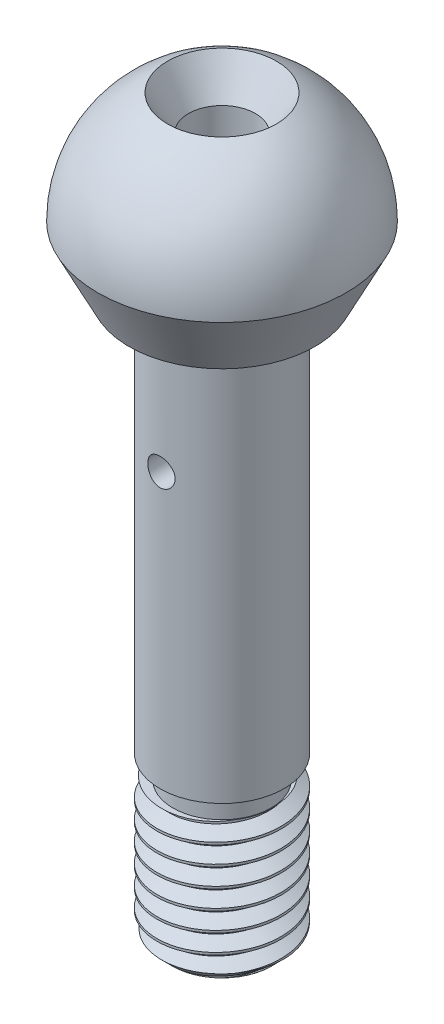
SolidWorks part; units mm, degrees
ref_plane "Front Plane" through (0, 0, 0) normal (0, 0, 1) x (1, 0, 0)
ref_plane "Top Plane" through (0, 0, 0) normal (0, 1, 0) x (1, 0, 0)
ref_plane "Right Plane" through (0, 0, 0) normal (1, 0, 0) x (0, 0, -1)
sketch "Sketch2" plane through (0, 0, 0) normal (0, 0, 1) x (1, 0, 0)
  line L0 (0, 12.7) -> (0, -63.5)
  line L1 (12.7, 0) -> (9.525, 0) construction
  line L2 (0, 0) -> (9.525, 0) construction
  line L3 (12.7, 0) -> (9.525, -6.35)
  line L5 (9.525, 0) -> (9.525, -6.35) construction
  line L6 (9.525, -6.35) -> (6.35, -6.35)
  line L7 (6.35, -6.35) -> (6.35, -63.5)
  line L8 (6.35, -63.5) -> (0, -63.5)
  arc A0 (12.7, 0) -> (0, 12.7) centre (0, 0) ccw
  dimension "D1" = 12.7
  dimension "D2" = 76.2
  dimension "D4" = 6.35
  dimension "D5" = 3.175
revolve "Revolve2" add sketch "Sketch2" angle 360 about L0
ref_plane "Plane1" through (0, 12.7, 0) normal (0, 1, 0) x (1, 0, 0)
sketch "Sketch6" plane through (0, 12.7, 0) normal (0, 1, 0) x (1, 0, 0)
  circle A0 centre (0, 0) radius 6.35
extrude "Cut-Extrude2" cut sketch "Sketch6" against normal blind 5.08 draft 31
ref_plane "Plane2" through (0, 0, 12.7) normal (0, 0, 1) x (1, 0, 0)
sketch "Sketch7" plane through (0, 0, 12.7) normal (0, 0, 1) x (1, 0, 0)
  circle A0 centre (0, -19.05) radius 1.397
  dimension "D1" = 19.05
extrude "Cut-Extrude3" cut sketch "Sketch7" against normal through all contours A0
sketch "Sketch8" plane through (0, 7.62, 0) normal (0, 1, 0) x (1, 0, 0)
  circle A0 centre (0, 0) radius 3.429
  dimension "D1" = 6.858
extrude "Cut-Extrude4" cut sketch "Sketch8" against normal blind 31.75 and the other way through all
chamfer "Chamfer1" distance 1.27 angle 45 1 edges at (-6.35, -63.5, 0)
sketch "Sketch10" plane through (0, -63.5, 0) normal (0, -1, 0) x (1, 0, 0)
  circle A0 centre (0, 0) radius 6.35
curve "Helix/Spiral1" pitch 1.9538 height 15.6308 radius 6.35 centre (0, -63.5, 0) axis (0, 1, 0) start towards (0, 0, 1)
sketch "Sketch11" plane through (0, 0, 0) normal (1, 0, 0) x (0, 0, -1)
  line L0 (-6.35, -62.7668) -> (-6.35, -64.7206) construction
  line L1 (-6.35, -64.7206) -> (-6.35, -64.4769) construction
  line L2 (-6.35, -64.4769) -> (-6.944, -64.4769)
  line L3 (-6.35, -64.4769) -> (-5.08, -63.7437)
  line L4 (-5.08, -63.7437) -> (-5.08, -63.5)
  line L5 (-5.08, -63.5) -> (-6.35, -62.7668)
  line L6 (-6.944, -64.4769) -> (-6.944, -62.7668)
  line L7 (-6.944, -62.7668) -> (-6.35, -62.7668)
  line L8 (-5.08, -63.5) -> (5.08, -63.5) construction
  line L19 (-6.35, -20.447) -> (-6.35, -62.23) construction
  dimension "D1" = 1.9538
  dimension "D2" = 60
  dimension "D3" = 60
  dimension "D4" = 1.27
sweep "Cut-Sweep2" cut profiles "Sketch11" path "Helix/Spiral1"
sketch "Sketch12" plane through (0, 0, 0) normal (-1, 0, 0) x (0, 0, 1)
  line L2 (5.0165, -47.136) -> (7.6835, -47.136)
  line L3 (5.0165, -47.136) -> (5.0165, -49.5172)
  line L4 (5.0165, -49.5172) -> (7.6835, -49.5172)
  line L5 (7.6835, -47.136) -> (7.6835, -49.5172)
  point P0 (6.35, -47.136)
  dimension "D1" = 2.667
  dimension "D2" = 2.3813
revolve "Cut-Revolve1" cut sketch "Sketch12" angle 360 about axis through (0, 12.7, 0) along (0, 1, 0)
